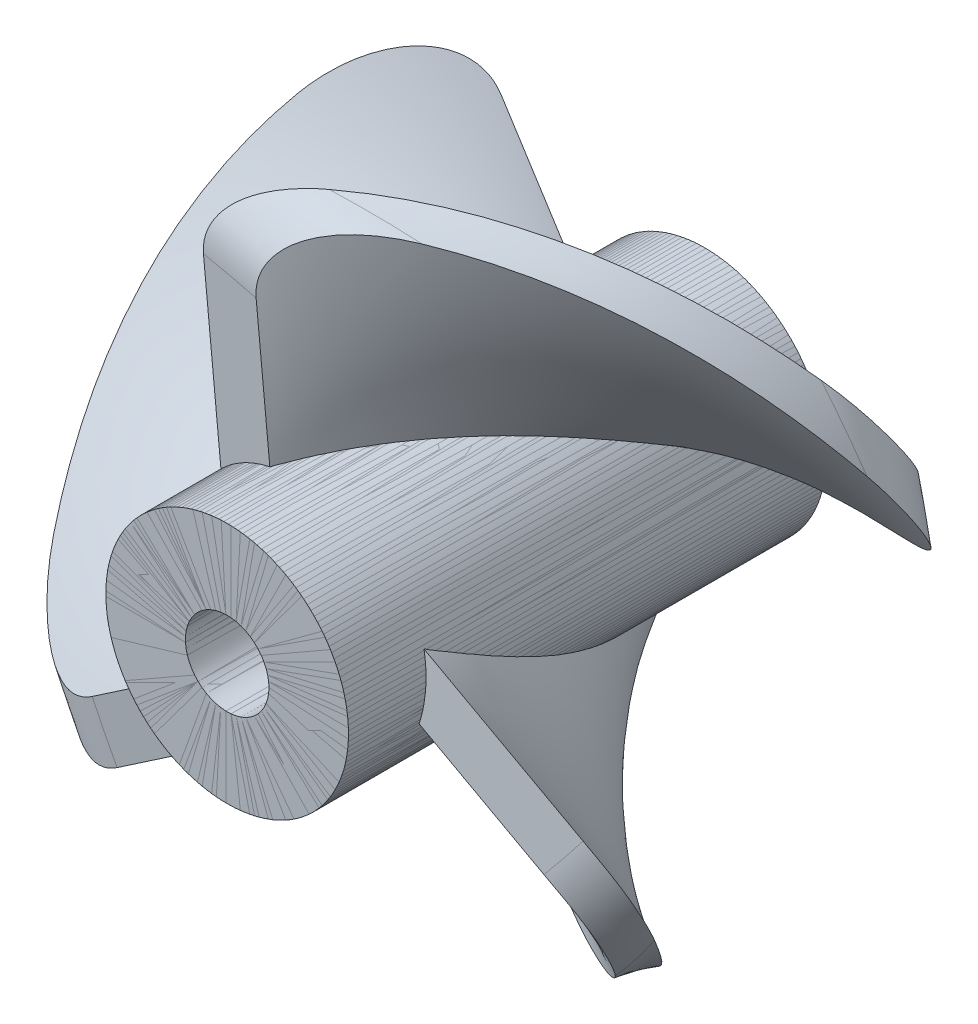
SolidWorks part; units mm, degrees
ref_plane "前视基准面" through (0, 0, 0) normal (0, 0, 1) x (1, 0, 0)
ref_plane "上视基准面" through (0, 0, 0) normal (0, 1, 0) x (1, 0, 0)
ref_plane "右视基准面" through (0, 0, 0) normal (1, 0, 0) x (0, 0, -1)
sketch "草图2" plane through (0, 0, 0) normal (0, 0, 1) x (1, 0, 0)
  circle A0 centre (-9.75, -28) radius 1.05
  dimension "D1" = 2.1
extrude "拉伸-薄壁1" add sketch "草图2" along normal blind 12 thin
ref_plane "5mm基准面" through (0, 0, 10) normal (0, 0, 1) x (1, 0, 0)
sketch "草图3" plane through (0, 0, 10) normal (0, 0, 1) x (1, 0, 0)
  circle A0 centre (-9.75, -28) radius 3.05 construction
  circle A1 centre (-9.75, -28) radius 3.05
curve "螺旋线/涡状线1" pitch 34 height 8.84 turns 0.26
sketch3d "3D草图3"
  line L2 (-7.4622, -25.983, 1.16) -> (-7.4622, -27.385, 1.264)
  line L3 (-7.4622, -25.983, 1.16) -> (-1.4922, -25.9697, 1.3409)
  line L4 (-1.4922, -25.9697, 1.3409) -> (-1.4923, -27.3717, 1.4449)
  line L5 (-7.4622, -27.385, 1.264) -> (-1.4923, -27.3717, 1.4449)
  spline S0 degree 3 poles (-11.9067, -25.8433, 10) (-11.6136, -25.5502, 9.2646) (-10.9042, -25.084, 7.7895) (-9.6515, -24.8657, 5.58) (-8.4149, -25.1623, 3.3705) (-7.7363, -25.6721, 1.8954) (-7.4622, -25.983, 1.16) knots 0 0 0 0 0.25 0.5 0.75 1 1 1 1 construction
  point P0 (-7.4247, -25.9499, 1.16)
ref_plane "基准面6" through (0.0163, -0.0398, -0.5367) normal (0.0304, -0.0739, -0.9968) x (-0.9995, -0.0022, -0.0303)
sweep "扫描4" add profiles "3D草图3" path "螺旋线/涡状线1"
fillet "圆角2" radius 2 2 edges
pattern_circular "阵列(圆周)3" count 3 over 360 about axis through (-9.75, -28, 12) along (0, 0, 1) of bodies 106
